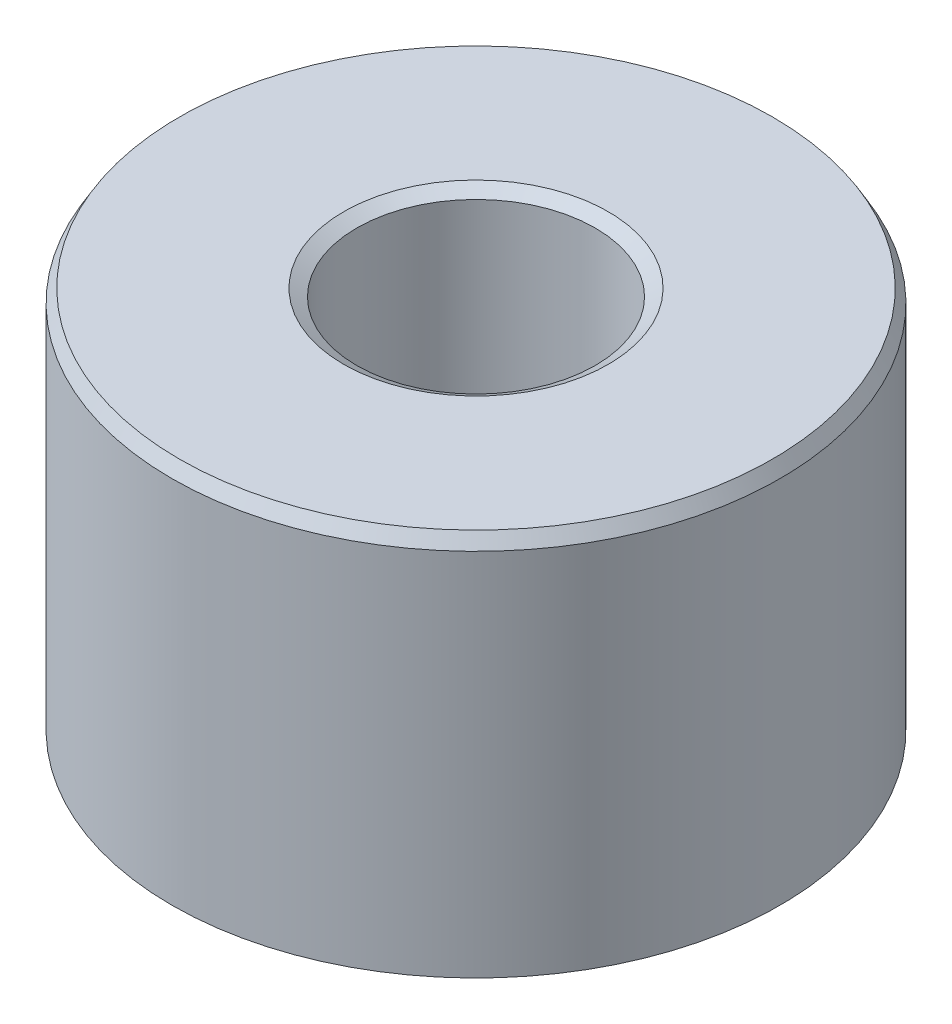
SolidWorks part; units mm, degrees
ref_plane "Front Plane" through (0, 0, 0) normal (0, 0, 1) x (1, 0, 0)
ref_plane "Top Plane" through (0, 0, 0) normal (0, 1, 0) x (1, 0, 0)
ref_plane "Right Plane" through (0, 0, 0) normal (1, 0, 0) x (0, 0, -1)
sketch "Sketch1" plane through (0, 0, 0) normal (0, 1, 0) x (1, 0, 0)
  circle A0 centre (0, 0) radius 60
  dimension "SLEEVE_OD" = 120
extrude "Boss-Extrude1" add sketch "Sketch1" along normal blind 76.9967
sketch "Sketch2" plane through (0, 0, 0) normal (0, 1, 0) x (1, 0, 0)
  circle A0 centre (0, 0) radius 23.5256
  dimension "BORE_D" = 47.0513
extrude "Cut-Extrude1" cut sketch "Sketch2" along normal through all
chamfer "Chamfer1" distance 2.5838 angle 30 4 edges at (0, 76.9967, 23.5256) (0, 0, 23.5256) (0, 0, 60) (0, 76.9967, 60) first distance on face at (0, 76.9967, 23.5256) first distance on face at (0, 0, 23.5256) first distance on face at (0, 76.9967, 60)
